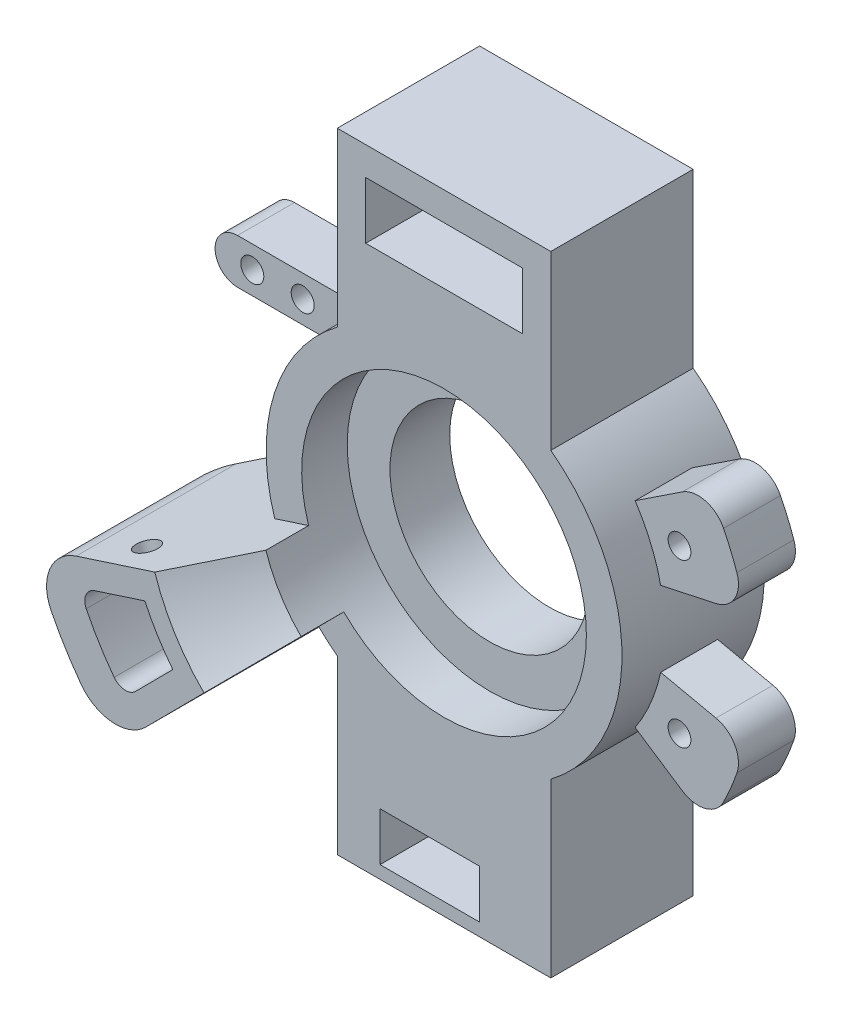
SolidWorks part; units mm, degrees
ref_plane "Front Plane" through (0, 0, 0) normal (0, 0, 1) x (1, 0, 0)
ref_plane "Top Plane" through (0, 0, 0) normal (0, 1, 0) x (1, 0, 0)
ref_plane "Right Plane" through (0, 0, 0) normal (1, 0, 0) x (0, 0, -1)
sketch "Sketch1" plane through (0, 0, 0) normal (0, 1, 0) x (1, 0, 0)
  line L1 (-37.5, -25) -> (37.5, -25)
  line L2 (-37.5, -25) -> (-37.5, 25)
  line L3 (-37.5, 25) -> (37.5, 25)
  line L4 (37.5, -25) -> (37.5, 25)
  line L5 (-37.5, -25) -> (37.5, 25) construction
  line L6 (-37.5, 25) -> (37.5, -25) construction
  point P0 (0, 0)
  dimension "D1" = 50
  dimension "D2" = 75
extrude "BE - main upright body" add sketch "Sketch1" along normal blind 221 contours L3 L4 L1 L2
sketch "Sketch2" plane through (0, 0, 25) normal (0, 0, 1) x (1, 0, 0)
  line L0 (-37.5, 221) -> (37.5, 0) construction
  line L1 (-37.5, 0) -> (37.5, 221) construction
  circle A0 centre (0, 110.5) radius 50
  point P10 (0, 110.5)
  dimension "D1" = 100
sketch "Sketch3" plane through (0, 0, -25) normal (0, 0, -1) x (-1, 0, 0)
  line L0 (-37.5, 0) -> (37.5, 221) construction
  line L1 (-37.5, 221) -> (37.5, 0) construction
  circle A0 centre (0, 110.5) radius 55
  point P10 (0, 110.5)
  dimension "D1" = 110
sketch "Sketch19" plane through (0, 0, 25) normal (0, 0, 1) x (1, 0, 0)
  line L0 (-37.5, 221) -> (37.5, 0) construction
  line L1 (-37.5, 0) -> (37.5, 221) construction
  circle A0 centre (0, 110.5) radius 62.5
  point P11 (0, 110.5)
  dimension "D1" = 125
extrude "Boss-Extrude1" add sketch "Sketch19" against normal up to surface (50 mm away) up to face at (0, 110.5, -25)
sketch "Sketch4" plane through (0, 0, 25) normal (0, 0, 1) x (1, 0, 0)
  line L0 (-37.5, 221) -> (37.5, 0) construction
  line L1 (37.5, 221) -> (-37.5, 0) construction
  line L2 (-37.5, 0) -> (37.5, 0) construction
  circle A0 centre (0, 110.5) radius 35
  dimension "D1" = 70
extrude "CE - Through hole" cut sketch "Sketch4" against normal through all
extrude "CE - Inner bearing" cut sketch "Sketch2" against normal blind 16 contours A0
extrude "CE - Outer bearing" cut sketch "Sketch3" against normal blind 13 contours A0
sketch "Sketch23" plane through (0, 0, 0) normal (0, 0, 1) x (1, 0, 0)
  line L0 (41.6939, 138.0974) -> (77.5515, 161.8318)
  line L1 (48.8688, 121.0757) -> (90.8968, 130.171)
  line L2 (0, 110.5) -> (41.6939, 138.0974) construction
  line L3 (0, 110.5) -> (48.8688, 121.0757) construction
  line L6 (41.6939, 82.9026) -> (77.5515, 59.1682)
  line L7 (48.8688, 99.9243) -> (90.8968, 90.829)
  line L8 (0, 110.5) -> (230.7958, 110.5) construction
  line L9 (90.8968, 130.171) -> (90.8968, 90.829) construction
  line L10 (0, 110.5) -> (48.8688, 99.9243) construction
  line L11 (0, 110.5) -> (41.6939, 82.9026) construction
  arc A0 (41.6939, 138.0974) -> (48.8688, 121.0757) centre (0, 110.5) cw
  arc A1 (90.8968, 130.171) -> (77.5515, 161.8318) centre (0, 110.5) ccw
  arc A6 (41.6939, 82.9026) -> (48.8688, 99.9243) centre (0, 110.5) ccw
  arc A7 (90.8968, 90.829) -> (77.5515, 59.1682) centre (0, 110.5) cw
  circle A8 centre (0, 110.5) radius 50 construction
  point P1 (90.8968, 110.5)
extrude "BE - caliper mount v2" add sketch "Sketch23" along normal mid plane 20
sketch "Sketch24" plane through (0, 0, 0) normal (0, 0, 1) x (1, 0, 0)
  line L0 (-35.2168, 75.0066) -> (-81.1221, 28.7407)
  line L1 (-47.5666, 95.0916) -> (-109.5701, 75.0066)
  line L2 (0, 110.5) -> (-35.2168, 75.0066) construction
  line L3 (0, 110.5) -> (-47.5666, 95.0916) construction
  line L8 (0, 110.5) -> (230.7958, 110.5) construction
  arc A0 (-35.2168, 75.0066) -> (-47.5666, 95.0916) centre (0, 110.5) cw
  arc A1 (-109.5701, 75.0066) -> (-81.1221, 28.7407) centre (0, 110.5) ccw
  circle A2 centre (0, 110.5) radius 50 construction
  point P1 (-109.5701, 75.0066)
extrude "BE - tie rod mount v2" add sketch "Sketch24" along normal blind 60 and the other way blind 10
sketch "Sketch32" plane through (0, 0, 0) normal (0, 0, 1) x (1, 0, 0)
  line L0 (-40.309, 155.863) -> (-87.5312, 155.863)
  line L1 (-87.5312, 140.0836) -> (-40.309, 140.0836)
  line L2 (-40.309, 155.863) -> (-40.309, 140.0836)
  arc A0 (-87.5312, 155.863) -> (-87.5312, 140.0836) centre (-87.5312, 147.9733) ccw
  circle A1 centre (0, 110.5) radius 50 construction
  circle A2 centre (-82.3567, 147.9733) radius 4.0509
  circle A3 centre (-64.6408, 147.9733) radius 4.0509
  point P10 (-82.3567, 150.8583)
extrude "BE - temp sensor mount v3" add sketch "Sketch32" along normal mid plane 20
sketch "Sketch12" plane through (0, 0, 25) normal (0, 0, 1) x (1, 0, 0)
  line L0 (-12.5, 201) -> (12.5, 201) construction
  line L2 (-37.5, 221) -> (37.5, 221) construction
  circle A0 centre (-12.5, 201) radius 4
  circle A1 centre (12.5, 201) radius 4
  point P2 (0, 201)
  dimension "D1" = 8
  dimension "D2" = 20
  dimension "D3" = 25
sketch "Sketch26" plane through (0, 0, 0) normal (0, 0, 1) x (1, 0, 0)
  line L0 (61.0859, 123.7196) -> (90.8968, 130.171) construction
  line L1 (77.5515, 161.8318) -> (52.1174, 144.9968) construction
  line L2 (61.0859, 123.7196) -> (90.8968, 130.171) construction
  line L3 (77.5515, 161.8318) -> (52.1174, 144.9968) construction
  line L4 (77.5515, 161.8318) -> (61.0859, 123.7196) construction
  line L5 (52.1174, 144.9968) -> (90.8968, 130.171) construction
  line L6 (0, 110.5) -> (188.9632, 110.5) construction
  line L7 (61.0859, 97.2804) -> (90.8968, 90.829) construction
  line L8 (77.5515, 59.1682) -> (52.1174, 76.0032) construction
  line L9 (52.1174, 76.0032) -> (90.8968, 90.829) construction
  line L10 (77.5515, 59.1682) -> (61.0859, 97.2804) construction
  circle A0 centre (67.7039, 139.0379) radius 4
  arc A2 (61.0859, 123.7196) -> (52.1174, 144.9968) centre (0, 110.5) ccw construction
  arc A3 (90.8968, 130.171) -> (77.5515, 161.8318) centre (0, 110.5) ccw construction
  arc A4 (61.0859, 123.7196) -> (52.1174, 144.9968) centre (0, 110.5) ccw construction
  arc A5 (90.8968, 130.171) -> (77.5515, 161.8318) centre (0, 110.5) ccw construction
  arc A6 (90.8968, 90.829) -> (77.5515, 59.1682) centre (0, 110.5) cw construction
  arc A7 (61.0859, 97.2804) -> (52.1174, 76.0032) centre (0, 110.5) cw construction
  circle A8 centre (67.7039, 81.9621) radius 4
  point P7 (67.7039, 139.0379)
  point P16 (67.7039, 81.9621)
  dimension "D1" = 8
extrude "CE - caliper holes" cut sketch "Sketch26" against normal through all both and the other way through all contours A0 | A8
extrude "CE - top clevis holes" cut sketch "Sketch12" against normal through all
sketch "Sketch13" plane through (0, 0, 25) normal (0, 0, 1) x (1, 0, 0)
  line L0 (-37.5, 221) -> (37.5, 221) construction
  line L1 (-27.5, 191) -> (27.5, 191)
  line L2 (-27.5, 191) -> (-27.5, 211)
  line L3 (-27.5, 211) -> (27.5, 211)
  line L4 (27.5, 191) -> (27.5, 211)
  line L5 (-27.5, 191) -> (27.5, 211) construction
  line L6 (-27.5, 211) -> (27.5, 191) construction
  point P0 (0, 201)
  dimension "D1" = 20
  dimension "D2" = 55
  dimension "D3" = 20
extrude "CE - top clevis space" cut sketch "Sketch13" against normal blind 35 contours L3 L4 L1 L2
ref_plane "Top clevis plane" through (0, 0, 5) normal (0, 0, 1) x (1, 0, 0)
ref_point "Position of Top Clevis"
sketch "Sketch14" plane through (0, 0, 25) normal (0, 0, 1) x (1, 0, 0)
  line L1 (-22.48, 4.5) -> (2.52, 4.5)
  line L2 (-22.48, 4.5) -> (-22.48, 16.5)
  line L3 (-22.48, 16.5) -> (2.52, 16.5)
  line L4 (2.52, 4.5) -> (2.52, 16.5)
  line L5 (-22.48, 4.5) -> (2.52, 16.5) construction
  line L6 (-22.48, 16.5) -> (2.52, 4.5) construction
  point P0 (-9.98, 10.5)
  dimension "D1" = 9.98
  dimension "D2" = 190.5
  dimension "D3" = 12
  dimension "D4" = 25
extrude "CE - bottom clevis space" cut sketch "Sketch14" against normal through all
ref_plane "Bottom Clevis Plane" through (0, 0, -1.65) normal (0, 0, 1) x (1, 0, 0)
ref_point "Position of Bottom Clevis"
ref_plane "P - xy plane containing bottom clevis" through (0, 10.5, 0) normal (0, -1, 0) x (-1, 0, 0)
ref_plane "P - xy plane containing tie rod" through (0, 63.84, 0) normal (0, -1, 0) x (-1, 0, 0)
ref_plane "P - front of part" through (2.52, 4.5, 25) normal (0, 0, 1) x (1, 0, 0)
sketch "Sketch15" plane through (0, 0, 25) normal (0, 0, 1) x (1, 0, 0)
  line L0 (2.52, 4.5) -> (2.52, 16.5) construction
  line L1 (-22.48, 16.5) -> (2.52, 16.5)
  line L2 (-22.48, 16.5) -> (-22.48, 21.5)
  line L3 (-22.48, 21.5) -> (2.52, 21.5)
  line L4 (2.52, 16.5) -> (2.52, 21.5)
  dimension "D1" = 5
extrude "CE - expand bottom clevis" cut sketch "Sketch15" against normal through all
sketch "Sketch16" plane through (2.52, 4.5, 25) normal (0, 0, 1) x (1, 0, 0)
  line L0 (0, 17) -> (-25, 17) construction
  line L1 (0, 0) -> (10.0076, 0)
  line L2 (0, 0) -> (0, 17)
  line L3 (0, 17) -> (10.0076, 17)
  line L4 (10.0076, 0) -> (10.0076, 17)
  dimension "D1" = 10.0076
extrude "CE - widen bottom clevis" cut sketch "Sketch16" against normal through all and the other way through all
sketch "Sketch17" plane through (0, 63.84, 0) normal (0, -1, 0) x (-1, 0, 0)
  point P0 (73.48, -49.15)
  point P1 (9.98, 1.65)
  point P3 (9.98, 1.65)
  dimension "D1" = 63.5
  dimension "D2" = 50.8
ref_point "Position of Tie Rod"
sketch "Sketch18" [suppressed] plane through (0, 0, 55) normal (0, 0, 1) x (1, 0, 0)
  line L1 (-80.502, 57.0586) -> (-66.458, 57.0586)
  line L2 (-80.502, 57.0586) -> (-80.502, 70.6214)
  line L3 (-80.502, 70.6214) -> (-66.458, 70.6214)
  line L4 (-66.458, 57.0586) -> (-66.458, 70.6214)
  line L5 (-80.502, 57.0586) -> (-66.458, 70.6214) construction
  line L6 (-80.502, 70.6214) -> (-66.458, 57.0586) construction
  point P0 (-73.48, 63.84)
  point P2 (-73.48, 63.84)
chamfer "Chamfer1" distance 20 angle 45 1 edges at (-42.5925, 84.3107, 60)
chamfer "Chamfer2" distance 30 angle 45 1 edges at (-98.1122, 50.1728, -10)
sketch "Sketch28" plane through (-32.3953, 100.0061, 0) normal (-0.3082, 0.9513, 0) x (0.9513, 0.3082, 0)
  circle A0 centre (-50.2304, -49.15) radius 4
  point P0 (-50.2304, -49.15)
  dimension "D1" = 8
extrude "Cut-Extrude1" cut sketch "Sketch28" against normal up to next contours A0
sketch "Sketch29" plane through (0, 0, 60) normal (0, 0, 1) x (1, 0, 0)
  line L0 (-70.0705, 78.4191) -> (-93.0797, 70.9656)
  line L1 (-60.2509, 62.449) -> (-77.2861, 45.2799)
  line L2 (-66.5932, 88.9282) -> (-109.5701, 75.0066) construction
  line L3 (-81.1221, 28.7407) -> (-49.3035, 60.8093) construction
  line L4 (-93.0797, 70.9656) -> (-95.8305, 79.4573) construction
  line L6 (-77.2861, 45.2799) -> (-70.9498, 38.993) construction
  line L8 (-70.0705, 78.4191) -> (-77.2861, 45.2799) construction
  line L9 (-93.0797, 70.9656) -> (-60.2509, 62.449) construction
  arc A1 (-93.0797, 70.9656) -> (-77.2861, 45.2799) centre (0, 110.5) ccw
  arc A2 (-109.5701, 75.0066) -> (-81.1221, 28.7407) centre (0, 110.5) ccw construction
  arc A3 (-70.0705, 78.4191) -> (-60.2509, 62.449) centre (0, 110.5) ccw
  arc A4 (-66.5932, 88.9282) -> (-49.3035, 60.8093) centre (0, 110.5) ccw construction
  point P5 (-73.48, 63.84)
  point P12 (-72.8369, 65.7141)
  point P13 (-73.48, 63.84)
  point P20 (-73.48, 63.84)
  point P21 (-60.2509, 62.449)
extrude "Cut-Extrude2" cut sketch "Sketch29" against normal up to next
fillet "Fillet1" radius 10 4 edges at (77.5515, 59.1682, 0) (90.8968, 90.829, 0) (90.8968, 130.171, 0) (77.5515, 161.8318, 0)
fillet "Fillet2" radius 15 2 edges at (-81.1221, 28.7407, 40) (-109.5701, 75.0066, 40)
fillet "Fillet3" radius 5 2 edges at (-77.2861, 45.2799, 32.9761) (-93.0797, 70.9656, 32.9761)
sketch "Sketch30" [suppressed] plane through (0, 0, 10) normal (0, 0, 1) x (1, 0, 0)
  circle A0 centre (-70.5637, 142.1694) radius 2.5568
  circle A1 centre (-83.4108, 142.1694) radius 2.5568
equation "\"clevis_pin_y\"=20"
equation "\"D2@Sketch12\"=\"clevis_pin_y\""
equation "\"clevis_pin_dist\"=25"
equation "\"D3@Sketch12\"=\"clevis_pin_dist\""
equation "\"D2@Sketch13\"=\"clevis_pin_dist\" + 30"
equation "\"D1@Sketch13\"=\"clevis_pin_y\""
equation "\"x_dist_a_arms\"=9.98"
equation "\"D1@Sketch14\"=\"x_dist_a_arms\""
equation "\"y_dist_a_arms\"=190.5"
equation "\"D2@Sketch14\"=\"y_dist_a_arms\""
equation "\"y_dist_bottom_clevis_to_tie_rod\"= 53.34"
equation "\"x_dist_bottom_clevis_to_tie_rod\"= 63.50"
equation "\"z_dist_bottom_clevis_to_tie_rod\"= 50.80"
